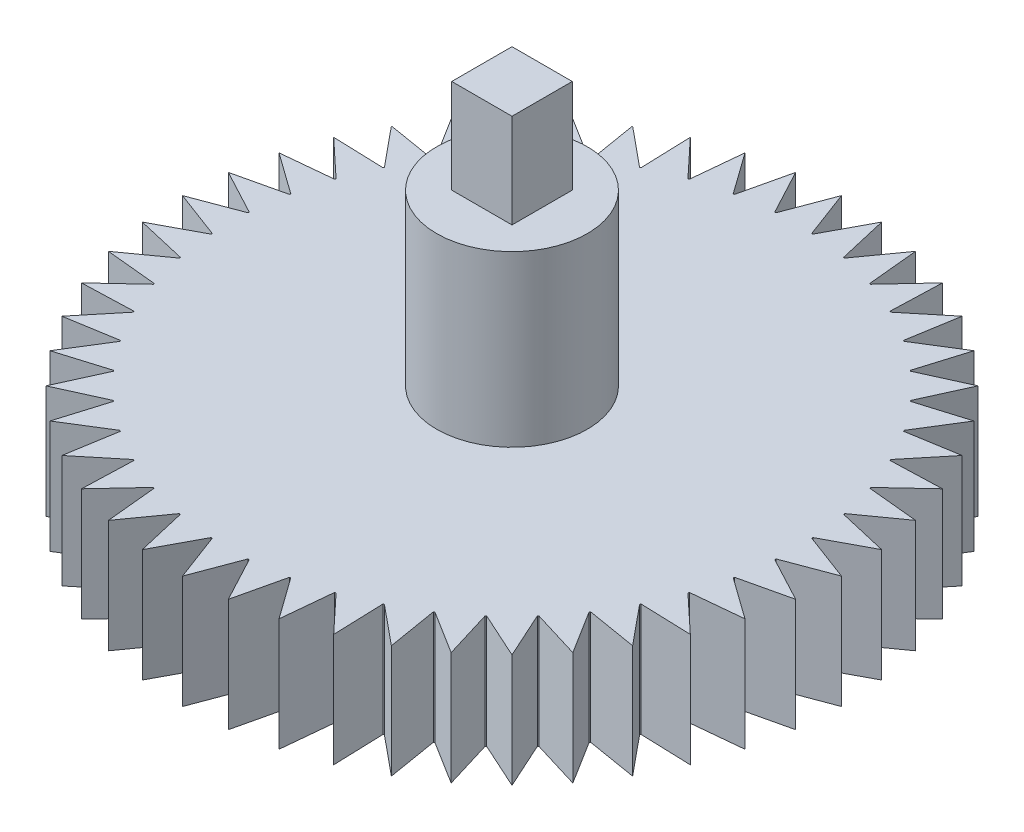
SolidWorks part; units mm, degrees
ref_plane "Спереди" through (0, 0, 0) normal (0, 0, 1) x (1, 0, 0)
ref_plane "Сверху" through (0, 0, 0) normal (0, 1, 0) x (1, 0, 0)
ref_plane "Справа" through (0, 0, 0) normal (1, 0, 0) x (0, 0, -1)
sketch "Эскиз1" plane through (0, 0, 0) normal (0, 1, 0) x (1, 0, 0)
  line L0 (2.2842, 17.3503) -> (2.8954, 14.7179)
  line L1 (1.0126, 14.9658) -> (2.2842, 17.3503)
  line L2 (4.5293, 16.9037) -> (4.7917, 14.2141)
  line L3 (2.9573, 14.7056) -> (4.5293, 16.9037)
  line L4 (0, 1.5) -> (2.2, 1.5)
  line L5 (0, 1.5) -> (-2.2, 1.5)
  line L6 (0, -1.5) -> (-2.2, -1.5)
  line L7 (0, -1.5) -> (2.2, -1.5)
  line L299 (6.697, 16.1679) -> (6.606, 13.467)
  line L303 (4.8515, 14.1938) -> (6.697, 16.1679)
  line L304 (0, 17.5) -> (0.9495, 14.9699)
  line L305 (-0.9495, 14.9699) -> (0, 17.5)
  line L306 (8.75, 15.1554) -> (8.3073, 12.4896)
  line L307 (6.6626, 13.4391) -> (8.75, 15.1554)
  line L308 (10.6533, 13.8837) -> (9.8664, 11.2984)
  line L309 (8.3598, 12.4545) -> (10.6533, 13.8837)
  line L310 (12.3744, 12.3744) -> (11.2567, 9.9139)
  line L311 (9.9139, 11.2567) -> (12.3744, 12.3744)
  line L312 (13.8837, 10.6533) -> (12.4545, 8.3598)
  line L313 (11.2984, 9.8664) -> (13.8837, 10.6533)
  line L314 (15.1554, 8.75) -> (13.4391, 6.6626)
  line L315 (12.4896, 8.3073) -> (15.1554, 8.75)
  line L316 (16.1679, 6.697) -> (14.1938, 4.8515)
  line L317 (13.467, 6.606) -> (16.1679, 6.697)
  line L318 (16.9037, 4.5293) -> (14.7056, 2.9573)
  line L319 (14.2141, 4.7917) -> (16.9037, 4.5293)
  line L320 (17.3503, 2.2842) -> (14.9658, 1.0126)
  line L321 (14.7179, 2.8954) -> (17.3503, 2.2842)
  line L322 (17.5, 0) -> (14.9699, -0.9495)
  line L323 (14.9699, 0.9495) -> (17.5, 0)
  line L324 (17.3503, -2.2842) -> (14.7179, -2.8954)
  line L325 (14.9658, -1.0126) -> (17.3503, -2.2842)
  line L326 (16.9037, -4.5293) -> (14.2141, -4.7917)
  line L327 (14.7056, -2.9573) -> (16.9037, -4.5293)
  line L328 (16.1679, -6.697) -> (13.467, -6.606)
  line L329 (14.1938, -4.8515) -> (16.1679, -6.697)
  line L330 (15.1554, -8.75) -> (12.4896, -8.3073)
  line L331 (13.4391, -6.6626) -> (15.1554, -8.75)
  line L332 (13.8837, -10.6533) -> (11.2984, -9.8664)
  line L333 (12.4545, -8.3598) -> (13.8837, -10.6533)
  line L334 (12.3744, -12.3744) -> (9.9139, -11.2567)
  line L335 (11.2567, -9.9139) -> (12.3744, -12.3744)
  line L336 (10.6533, -13.8837) -> (8.3598, -12.4545)
  line L337 (9.8664, -11.2984) -> (10.6533, -13.8837)
  line L338 (8.75, -15.1554) -> (6.6626, -13.4391)
  line L339 (8.3073, -12.4896) -> (8.75, -15.1554)
  line L340 (6.697, -16.1679) -> (4.8515, -14.1938)
  line L341 (6.606, -13.467) -> (6.697, -16.1679)
  line L342 (4.5293, -16.9037) -> (2.9573, -14.7056)
  line L343 (4.7917, -14.2141) -> (4.5293, -16.9037)
  line L344 (2.2842, -17.3503) -> (1.0126, -14.9658)
  line L345 (2.8954, -14.7179) -> (2.2842, -17.3503)
  line L346 (0, -17.5) -> (-0.9495, -14.9699)
  line L347 (0.9495, -14.9699) -> (0, -17.5)
  line L348 (-2.2842, -17.3503) -> (-2.8954, -14.7179)
  line L349 (-1.0126, -14.9658) -> (-2.2842, -17.3503)
  line L350 (-4.5293, -16.9037) -> (-4.7917, -14.2141)
  line L351 (-2.9573, -14.7056) -> (-4.5293, -16.9037)
  line L352 (-6.697, -16.1679) -> (-6.606, -13.467)
  line L353 (-4.8515, -14.1938) -> (-6.697, -16.1679)
  line L354 (-8.75, -15.1554) -> (-8.3073, -12.4896)
  line L355 (-6.6626, -13.4391) -> (-8.75, -15.1554)
  line L356 (-10.6533, -13.8837) -> (-9.8664, -11.2984)
  line L357 (-8.3598, -12.4545) -> (-10.6533, -13.8837)
  line L358 (-12.3744, -12.3744) -> (-11.2567, -9.9139)
  line L359 (-9.9139, -11.2567) -> (-12.3744, -12.3744)
  line L360 (-13.8837, -10.6533) -> (-12.4545, -8.3598)
  line L361 (-11.2984, -9.8664) -> (-13.8837, -10.6533)
  line L362 (-15.1554, -8.75) -> (-13.4391, -6.6626)
  line L363 (-12.4896, -8.3073) -> (-15.1554, -8.75)
  line L364 (-16.1679, -6.697) -> (-14.1938, -4.8515)
  line L365 (-13.467, -6.606) -> (-16.1679, -6.697)
  line L366 (-16.9037, -4.5293) -> (-14.7056, -2.9573)
  line L367 (-14.2141, -4.7917) -> (-16.9037, -4.5293)
  line L368 (-17.3503, -2.2842) -> (-14.9658, -1.0126)
  line L369 (-14.7179, -2.8954) -> (-17.3503, -2.2842)
  line L370 (-17.5, 0) -> (-14.9699, 0.9495)
  line L371 (-14.9699, -0.9495) -> (-17.5, 0)
  line L372 (-17.3503, 2.2842) -> (-14.7179, 2.8954)
  line L373 (-14.9658, 1.0126) -> (-17.3503, 2.2842)
  line L374 (-16.9037, 4.5293) -> (-14.2141, 4.7917)
  line L375 (-14.7056, 2.9573) -> (-16.9037, 4.5293)
  line L376 (-16.1679, 6.697) -> (-13.467, 6.606)
  line L377 (-14.1938, 4.8515) -> (-16.1679, 6.697)
  line L378 (-15.1554, 8.75) -> (-12.4896, 8.3073)
  line L379 (-13.4391, 6.6626) -> (-15.1554, 8.75)
  line L380 (-13.8837, 10.6533) -> (-11.2984, 9.8664)
  line L381 (-12.4545, 8.3598) -> (-13.8837, 10.6533)
  line L382 (-12.3744, 12.3744) -> (-9.9139, 11.2567)
  line L383 (-11.2567, 9.9139) -> (-12.3744, 12.3744)
  line L384 (-10.6533, 13.8837) -> (-8.3598, 12.4545)
  line L385 (-9.8664, 11.2984) -> (-10.6533, 13.8837)
  line L386 (-8.75, 15.1554) -> (-6.6626, 13.4391)
  line L387 (-8.3073, 12.4896) -> (-8.75, 15.1554)
  line L388 (-6.697, 16.1679) -> (-4.8515, 14.1938)
  line L389 (-6.606, 13.467) -> (-6.697, 16.1679)
  line L390 (-4.5293, 16.9037) -> (-2.9573, 14.7056)
  line L391 (-4.7917, 14.2141) -> (-4.5293, 16.9037)
  line L392 (-2.2842, 17.3503) -> (-1.0126, 14.9658)
  line L393 (-2.8954, 14.7179) -> (-2.2842, 17.3503)
  arc A0 (-2.2, 1.5) -> (-2.2, -1.5) centre (1.4803, 0) ccw
  arc A1 (2.2, 1.5) -> (2.2, -1.5) centre (-1.1791, 0) cw
  circle A3 centre (0, 0) radius 15
  point P158 (0, 0)
  point P224 (0, 0)
extrude "Бобышка-Вытянуть5" add sketch "Эскиз1" along normal blind 6 contours A3 | A3 L344 L345 | A3 L342 L343 | A3 L340 L341 | A3 L338 L339 | A3 L336 L337 | A3 L334 L335 | A3 L346 L347 | A3 L348 L349 | A3 L350 L351 | A3 L352 L353 | A3 L354 L355 | A3 L356 L357 | A3 L358 L359 | A3 L360 L361 | A3 L362 L363 | A3 L364 L365 | A3 L366 L367 | A3 L368 L369 | A3 L370 L371 | A3 L372 L373 | A3 L374 L375 | A3 L376 L377 | A3 L378 L379 | A3 L380 L381 | A3 L382 L383 | A3 L384 L385 | A3 L386 L387 | A3 L388 L389 | A3 L390 L391 | A3 L392 L393 | A3 L304 L305 | A3 L0 L1 | A3 L2 L3 | A3 L299 L303 | A3 L306 L307 | A3 L308 L309 | A3 L310 L311 | A3 L312 L313 | A3 L314 L315 | A3 L316 L317 | A3 L318 L319 | A3 L320 L321 | A3 L322 L323 | A3 L324 L325 | A3 L326 L327 | A3 L328 L329 | A3 L330 L331 | A3 L332 L333 region at (2.0658, 0, -15.6913) region at (2.8436, 0, -14.2957) region at (4.0962, 0, -15.2874) region at (0, 0, -15.8267) region at (6.0566, 0, -14.6219) region at (-2.0658, 0, -15.6913) region at (7.9133, 0, -13.7063) region at (-4.0962, 0, -15.2874) region at (9.6347, 0, -12.5561) region at (-6.0566, 0, -14.6219) region at (11.1911, 0, -11.1911) region at (-7.9133, 0, -13.7063) region at (12.5561, 0, -9.6347) region at (-9.6347, 0, -12.5561) region at (13.7063, 0, -7.9133) region at (-11.1911, 0, -11.1911) region at (14.6219, 0, -6.0566) region at (-12.5561, 0, -9.6347) region at (15.2874, 0, -4.0962) region at (-13.7063, 0, -7.9133) region at (15.6913, 0, -2.0658) region at (-14.6219, 0, -6.0566) region at (15.8267, 0, 0) region at (-15.2874, 0, -4.0962) region at (-15.6913, 0, -2.0658) region at (15.6913, 0, 2.0658) region at (-15.8267, 0, 0) region at (15.2874, 0, 4.0962) region at (-15.6913, 0, 2.0658) region at (14.6219, 0, 6.0566) region at (-15.2874, 0, 4.0962) region at (13.7063, 0, 7.9133) region at (-14.6219, 0, 6.0566) region at (12.5561, 0, 9.6347) region at (-13.7063, 0, 7.9133) region at (11.1911, 0, 11.1911) region at (-12.5561, 0, 9.6347) region at (9.6347, 0, 12.5561) region at (-11.1911, 0, 11.1911) region at (7.9133, 0, 13.7063) region at (-9.6347, 0, 12.5561) region at (6.0566, 0, 14.6219) region at (-7.9133, 0, 13.7063) region at (4.0962, 0, 15.2874) region at (-6.0566, 0, 14.6219) region at (2.0658, 0, 15.6913) region at (-4.0962, 0, 15.2874) region at (0, 0, 15.8267) region at (-2.0658, 0, 15.6913)
extrude "Бобышка-Вытянуть6" add sketch "Эскиз1<5>" along normal blind 6 contours L6 A0 L5 L4 A1 L7
sketch "Эскиз1<5>" plane through (0, 0, 0) normal (0, 1, 0) x (1, 0, 0) same geometry as "Эскиз1"
ref_plane "Плоскость3" through (0, 6, 0) normal (0, 1, 0) x (1, 0, 0)
ref_plane "Плоскость4" through (0, 15, 0) normal (0, -1, 0) x (-1, 0, 0)
sketch "Эскиз5" plane through (0, 15, 0) normal (0, -1, 0) x (-1, 0, 0)
  line L0 (-1.6, 1.6) -> (1.6, 1.6)
  line L2 (1.6, 1.6) -> (1.6, -1.6)
  line L3 (1.6, -1.6) -> (-1.6, -1.6)
  line L4 (-1.6, -1.6) -> (-1.6, 1.6)
  point P0 (0, 0)
sketch "Эскиз4" plane through (0, 6, 0) normal (0, 1, 0) x (1, 0, 0)
  circle A0 centre (0, 0) radius 4
ref_plane "Плоскость5" through (0, 0, 0) normal (0, -1, 0) x (-1, 0, 0)
sketch "Эскиз6" plane through (0, 0, 0) normal (0, -1, 0) x (-1, 0, 0)
  circle A0 centre (0, 0) radius 4
extrude "Бобышка-Вытянуть9" add sketch "Эскиз6" along normal blind 5
extrude "Бобышка-Вытянуть10" add sketch "Эскиз4" along normal blind 9
extrude "Бобышка-Вытянуть11" add sketch "Эскиз5" against normal blind 5
